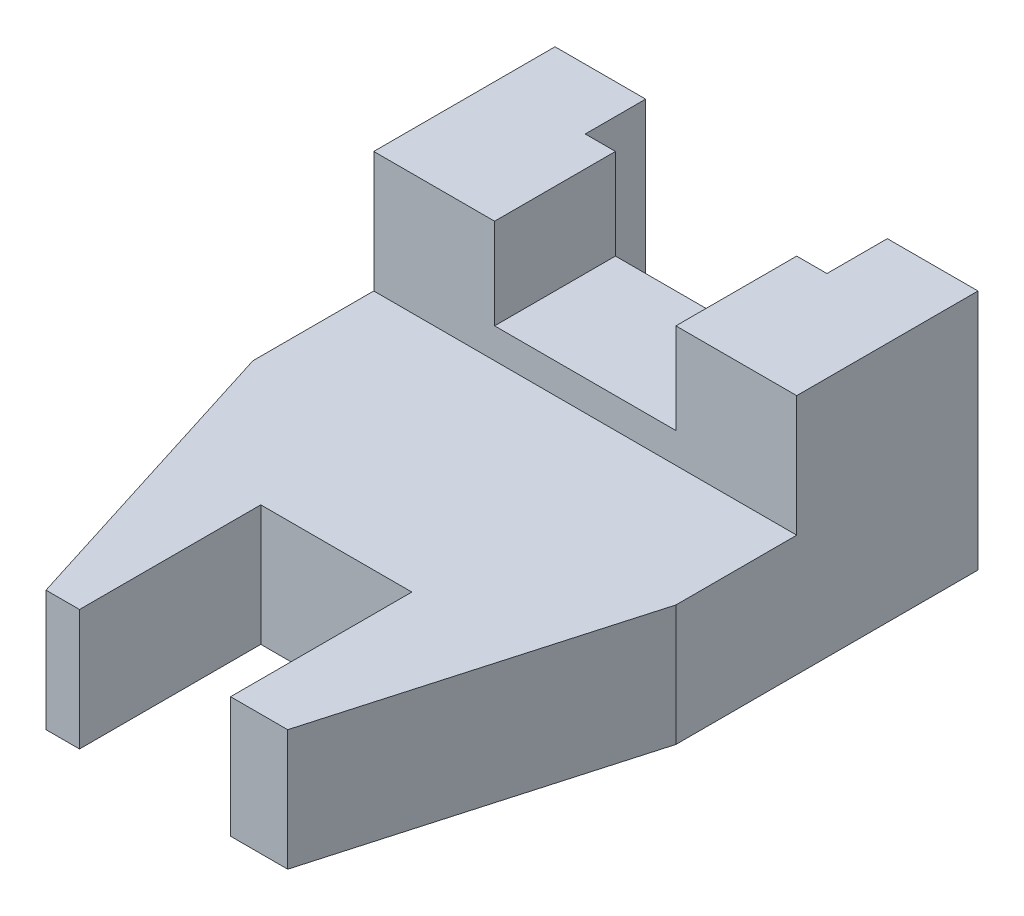
SolidWorks part; units mm, degrees
ref_plane "Front Plane" through (0, 0, 0) normal (0, 0, 1) x (1, 0, 0)
ref_plane "Top Plane" through (0, 0, 0) normal (0, 1, 0) x (1, 0, 0)
ref_plane "Right Plane" through (0, 0, 0) normal (1, 0, 0) x (0, 0, -1)
sketch "Sketch1" plane through (0, 0, 0) normal (0, 1, 0) x (1, 0, 0)
  line L0 (0, 0) -> (5.5455, 0)
  line L1 (5.5455, 0) -> (5.5455, 30)
  line L2 (5.5455, 30) -> (30.5455, 30)
  line L3 (30.5455, 30) -> (30.5455, 0)
  line L4 (30.5455, 0) -> (40, 0)
  line L5 (40, 0) -> (54.2424, 50)
  line L6 (54.2424, 50) -> (54.2424, 100)
  line L7 (54.2424, 100) -> (39.2424, 100)
  line L8 (39.2424, 100) -> (39.2424, 90)
  line L10 (-0.7576, 90) -> (-0.7576, 100)
  line L11 (-0.7576, 100) -> (-15.7576, 100)
  line L12 (-15.7576, 100) -> (-15.7576, 50)
  line L13 (-15.7576, 50) -> (0, 0)
  line L14 (39.2424, 90) -> (34.2424, 90)
  line L15 (34.2424, 90) -> (34.2424, 70)
  line L16 (34.2424, 70) -> (4.2424, 70)
  line L17 (4.2424, 70) -> (4.2424, 90)
  line L18 (4.2424, 90) -> (-0.7576, 90)
  point P10 (17.9394, 132.7273)
  point P20 (17.4545, 132.2424)
  point P21 (39.2424, 95)
  dimension "D1" = 40
  dimension "D2" = 50
  dimension "D3" = 50
  dimension "D4" = 30
  dimension "D5" = 25
  dimension "D6" = 70
  dimension "D7" = 50
  dimension "D8" = 50
  dimension "D9" = 30
  dimension "D10" = 10
  dimension "D11" = 40
  dimension "D12" = 20
  dimension "D13" = 15
  dimension "D14" = 5
  dimension "D15" = 5
  dimension "D16" = 20
  dimension "D17" = 10
extrude "Boss-Extrude1" add sketch "Sketch1" along normal blind 20
sketch "Sketch2" plane through (0, 20, 0) normal (0, 1, 0) x (1, 0, 0)
  line L0 (-15.7576, 100) -> (-0.7576, 100)
  line L1 (-0.7576, 100) -> (-0.7576, 90)
  line L2 (-0.7576, 90) -> (4.2424, 90)
  line L3 (4.2424, 90) -> (4.2424, 70)
  line L4 (4.2424, 70) -> (-15.7576, 70)
  line L5 (-15.7576, 100) -> (-15.7576, 50) construction
  line L6 (-15.7576, 70) -> (-15.7576, 100)
  line L7 (54.2424, 100) -> (39.2424, 100)
  line L8 (39.2424, 100) -> (39.2424, 90)
  line L9 (39.2424, 90) -> (34.2424, 90)
  line L10 (34.2424, 90) -> (34.2424, 70)
  line L11 (34.2424, 70) -> (54.2424, 70)
  line L12 (54.2424, 50) -> (54.2424, 100) construction
  line L13 (54.2424, 70) -> (54.2424, 100)
extrude "Boss-Extrude7" add sketch "Sketch2" along normal blind 20 and the other way blind 20 contours L6 L0 L1 L2 L3 L4 | L13 L7 L8 L9 L10 L11
sketch "Sketch5" plane through (0, 20, 0) normal (0, 1, 0) x (1, 0, 0)
  line L0 (4.2424, 70) -> (4.2424, 90)
  line L1 (4.2424, 90) -> (34.2424, 90)
  line L2 (34.2424, 90) -> (34.2424, 70)
  line L3 (34.2424, 70) -> (4.2424, 70)
extrude "Boss-Extrude12" add sketch "Sketch5" against normal blind 20 contours L3 L0 L1 L2
sketch "Sketch6" plane through (0, 20, 0) normal (0, 1, 0) x (1, 0, 0)
  line L0 (4.2424, 70) -> (34.2424, 70)
  line L1 (34.2424, 70) -> (34.2424, 90)
  line L2 (34.2424, 90) -> (4.2424, 90)
  line L3 (4.2424, 90) -> (4.2424, 70)
extrude "Boss-Extrude13" add sketch "Sketch6" along normal blind 5
